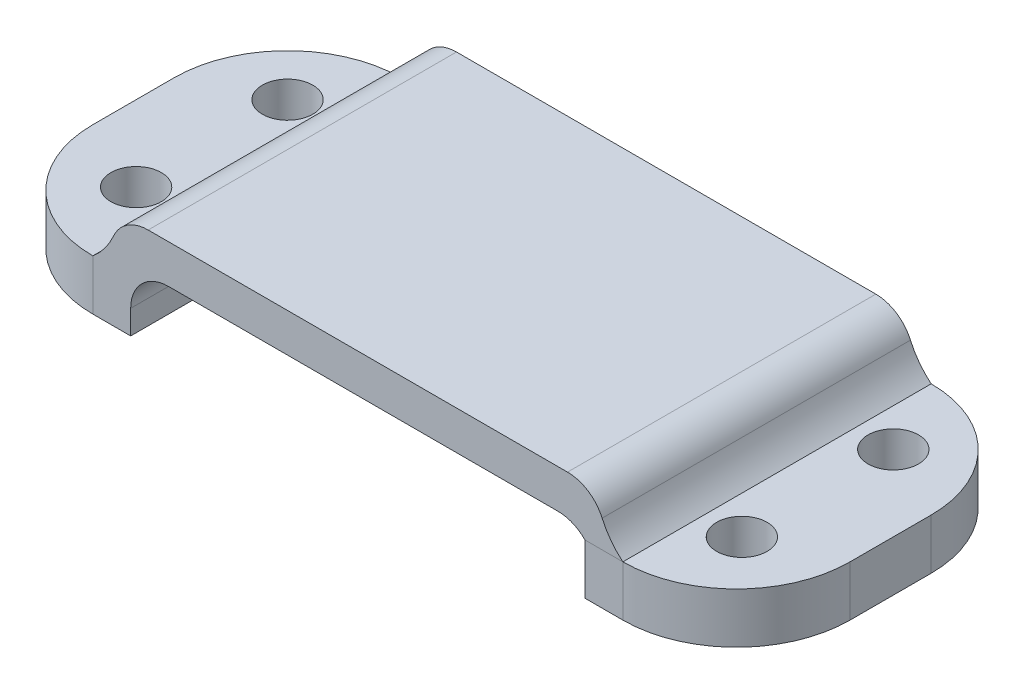
SolidWorks part; units mm, degrees
ref_plane "Front Plane" through (0, 0, 0) normal (0, 0, 1) x (1, 0, 0)
ref_plane "Top Plane" through (0, 0, 0) normal (0, 1, 0) x (1, 0, 0)
ref_plane "Right Plane" through (0, 0, 0) normal (1, 0, 0) x (0, 0, -1)
sketch "Sketch2" plane through (0, 0, 0) normal (0, 1, 0) x (1, 0, 0)
  line L0 (-18, 12.215) -> (-30, 12.215)
  line L1 (30, -12.215) -> (18, -12.215)
  line L2 (30, -12.215) -> (30, 12.215)
  line L3 (30, 12.215) -> (18, 12.215)
  line L4 (-30, -12.215) -> (-30, 12.215)
  line L5 (30, -12.215) -> (18, -7.329) construction
  line L6 (30, 12.215) -> (18, 7.329) construction
  line L7 (-30, 12.215) -> (-18, 12.215)
  line L8 (-30, 12.215) -> (-30, -12.215)
  line L9 (-30, -12.215) -> (-18, -12.215)
  line L10 (-18, 12.215) -> (-18, -12.215)
  line L11 (30, 12.215) -> (18, 12.215)
  line L12 (30, 12.215) -> (30, -12.215)
  line L13 (30, -12.215) -> (18, -12.215)
  line L14 (18, 12.215) -> (18, -12.215)
  line L15 (0, 0) -> (-30, -12.215) construction
  line L16 (0, 0) -> (-30, 12.215) construction
  line L17 (-18, -12.215) -> (-30, -12.215)
  point P0 (0, 0)
extrude "Boss-Extrude1" add sketch "Sketch2" along normal blind 4 contours L10 L0 L4 L9 | L3 L14 L1 L2 region at (-24, 0, 0) region at (24, 0, 0)
sketch "Sketch3" plane through (0, 4, 0) normal (0, 1, 0) x (1, 0, 0)
  line L0 (-18, 12.215) -> (-30, 12.215) construction
  circle A0 centre (-24, 6.215) radius 2
  circle A1 centre (24, 6.215) radius 2
  circle A2 centre (24, -5.785) radius 2
  circle A3 centre (-24, -5.785) radius 2
  dimension "D1" = 6
  dimension "D2" = 2
  dimension "D3" = 2
extrude "Cut-Extrude1" cut sketch "Sketch3" against normal blind 4
fillet "Fillet1" radius 9 2 edges at (-30, 2, 12.215) (-30, 2, -12.215)
fillet "Fillet2" radius 9 2 edges at (30, 2, -12.215) (30, 2, 12.215)
sketch "Sketch4" plane through (0, 0, 0) normal (0, 0, 1) x (1, 0, 0)
  line L5 (-21, 4) -> (-19.6147, 4.9)
  line L6 (-18, 4) -> (-21, 4)
  line L7 (-18, 4) -> (-18, 4.9)
  line L8 (-18, 4.9) -> (-19.6147, 4.9)
  line L11 (-18, 4.9) -> (-19.6147, 4.9)
  line L12 (-18, 4.9) -> (-18, 7.9654)
  line L13 (-18, 7.9654) -> (-19.6147, 7.9654)
  line L14 (-19.6147, 4.9) -> (-19.6147, 7.9654)
  line L15 (-18, 7.9654) -> (0, 7.9654)
  line L16 (-18, 7.9654) -> (-18, 4.9)
  line L17 (-18, 4.9) -> (0, 4.9)
  line L18 (0, 7.9654) -> (0, 4.9)
  point P2 (-19.6038, 8.522)
  point P5 (-19.6147, 8.9346)
  point P12 (-18, 8.7827)
  point P13 (-18, 8.5359)
  point P14 (-18, 8.422)
extrude "Boss-Extrude2" add sketch "Sketch4" along normal up to surface and the other way up to surface contours L18 L15 L12 L17 | L14 L8 L12 L13 | L7 L8 L5 L6 region at (-19.1883, 4.405, 0) region at (-18.8073, 6.4327, 0) region at (-9, 6.4327, 0) up to face at (-19.5, 2, 12.215) other way up to face at (-19.5, 2, -12.215)
mirror "Mirror1" about plane through (0, 0, 0) normal (1, 0, 0) of "Boss-Extrude2"
fillet "Fillet3" radius 3 4 edges at (19.6147, 7.9654, 0) (-19.6147, 7.9654, 0) (18, 4.9, 0) (-18, 4.9, 0)
fillet "Fillet4" radius 6 2 edges at (19.6147, 4.9, 0) (-19.6147, 4.9, 0)
